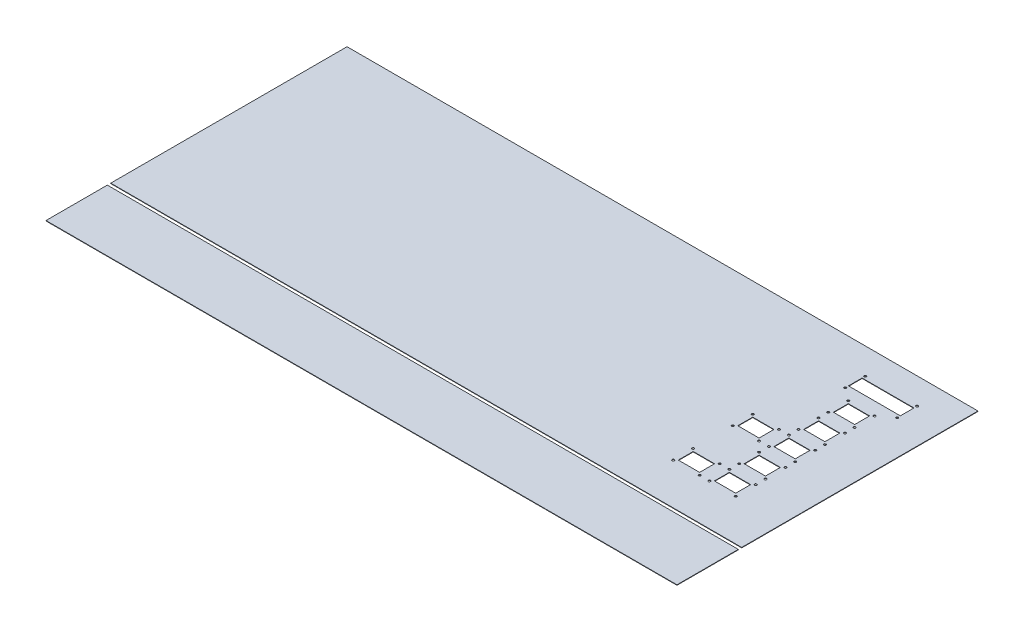
SolidWorks part; units mm, degrees
ref_plane "Front Plane" through (0, 0, 0) normal (0, 0, 1) x (1, 0, 0)
ref_plane "Top Plane" through (0, 0, 0) normal (0, 1, 0) x (1, 0, 0)
ref_plane "Right Plane" through (0, 0, 0) normal (1, 0, 0) x (0, 0, -1)
sketch "Sketch1" plane through (0, 0, 0) normal (0, 1, 0) x (1, 0, 0)
  line L1 (-736.6, -195.9) -> (736.6, -195.9)
  line L2 (-736.6, -195.9) -> (-736.6, 348.3)
  line L3 (-736.6, 348.3) -> (736.6, 348.3)
  line L4 (736.6, -195.9) -> (736.6, 348.3)
  line L5 (-736.6, -195.9) -> (736.6, 348.3) construction
  line L6 (-736.6, 348.3) -> (736.6, -195.9) construction
  line L11 (-736.6, -348.3) -> (736.6, -348.3)
  line L12 (-736.6, -348.3) -> (-736.6, -215.9)
  line L13 (-736.6, -215.9) -> (736.6, -215.9)
  line L14 (736.6, -348.3) -> (736.6, -215.9)
  point P0 (0, 0)
extrude "Boss-Extrude1" add sketch "Sketch1" along normal blind 0.508 and the other way blind 0.508
sketch "Sketch2" plane through (0, 0, 0) normal (0, 1, 0) x (1, 0, 0)
  line L5 (-736.6, 348.3) -> (736.6, 348.3)
  line L6 (-736.6, 348.3) -> (-736.6, -195.9)
  line L11 (-736.6, -195.9) -> (736.6, -195.9)
  line L12 (736.6, 348.3) -> (736.6, -195.9)
  line L13 (-736.6, -215.9) -> (736.6, -215.9)
  line L14 (-736.6, -215.9) -> (-736.6, -348.3)
  line L15 (-736.6, -348.3) -> (736.6, -348.3)
  line L16 (736.6, -215.9) -> (736.6, -348.3)
  line L17 (-742.6, 354.3) -> (742.6, 354.3)
  line L18 (-742.6, 354.3) -> (-742.6, -201.9)
  line L19 (-742.6, -201.9) -> (742.6, -201.9)
  line L20 (742.6, 354.3) -> (742.6, -201.9)
  line L21 (742.6, -354.3) -> (-742.6, -354.3)
  line L22 (742.6, -354.3) -> (742.6, -209.9)
  line L23 (742.6, -209.9) -> (-742.6, -209.9)
  line L24 (-742.6, -354.3) -> (-742.6, -209.9)
  dimension "D1" = 6
  dimension "D2" = 6
  dimension "D3" = 6
  dimension "D4" = 6
  dimension "D5" = 6
  dimension "D6" = 6
extrude "Boss-Extrude2" add sketch "Sketch2" along normal up to surface and the other way up to surface up to face at (0, 0.508, -76.2) other way up to face at (0, -0.508, -76.2)
sketch "Sketch3" plane through (0, 0, 0) normal (0, 1, 0) x (1, 0, 0)
  line L0 (568.95, -104.45) -> (568.95, -98.45) construction
  line L1 (568.95, -98.45) -> (574.95, -98.45) construction
  line L2 (631.05, -57.35) -> (631.05, -63.35) construction
  line L3 (631.05, -63.35) -> (625.05, -63.35) construction
  line L5 (574.95, -98.45) -> (625.05, -98.45)
  line L6 (574.95, -98.45) -> (574.95, -63.35)
  line L7 (574.95, -63.35) -> (625.05, -63.35)
  line L8 (625.05, -98.45) -> (625.05, -63.35)
  circle A1 centre (568.95, -104.45) radius 2.6
  circle A2 centre (631.05, -104.45) radius 2.6
  circle A3 centre (631.05, -57.35) radius 2.6
  circle A4 centre (568.95, -57.35) radius 2.6
  dimension "D1" = 5.2
  dimension "D2" = 5.2
  dimension "D3" = 5.2
  dimension "D4" = 5.2
  dimension "D5" = 6
  dimension "D6" = 6
  dimension "D7" = 6
  dimension "D8" = 6
extrude "Cut-Extrude1" cut sketch "Sketch3" against normal through all both and the other way through all
pattern_linear "LPattern1" count 5 spacing 70 along (0, 0, -1) count 2 spacing 85 along (-1, 0, 0) skipping (1, 1), (3, 1), (4, 1) of "Cut-Extrude1"
sketch "Sketch4" plane through (0, 0, 0) normal (0, 1, 0) x (1, 0, 0)
  line L0 (661.05, 245.55) -> (661.05, 253.05) construction
  line L1 (538.95, 285.15) -> (538.95, 292.65) construction
  line L5 (661.05, 253.05) -> (538.95, 253.05)
  line L6 (661.05, 253.05) -> (661.05, 285.15)
  line L7 (661.05, 285.15) -> (538.95, 285.15)
  line L8 (538.95, 253.05) -> (538.95, 285.15)
  circle A0 centre (661.05, 245.55) radius 2.6
  circle A1 centre (661.05, 292.65) radius 2.6
  circle A2 centre (538.95, 245.55) radius 2.6
  circle A3 centre (538.95, 292.65) radius 2.6
  dimension "D1" = 5.2
  dimension "D2" = 5.2
  dimension "5.4" = 5.2
  dimension "D3" = 5.2
  dimension "D4" = 7.5
  dimension "D5" = 7.5
extrude "Cut-Extrude2" cut sketch "Sketch4" against normal through all both and the other way through all
